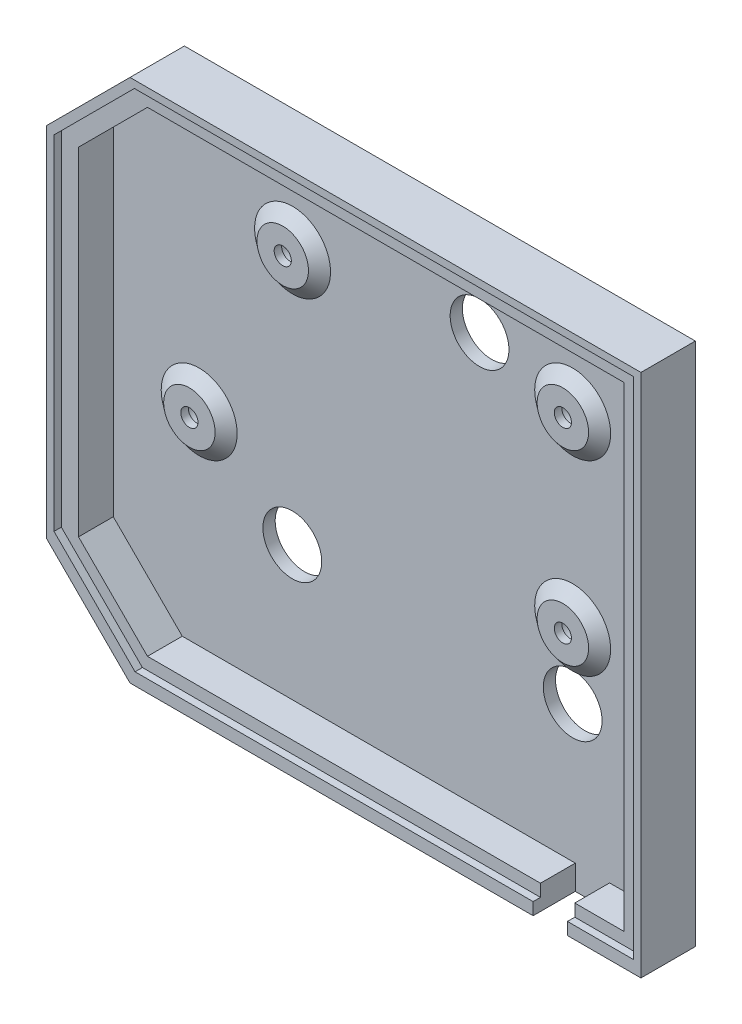
SolidWorks part; units mm, degrees
ref_plane "Plan de face" through (0, 0, 0) normal (0, 0, 1) x (1, 0, 0)
ref_plane "Plan de dessus" through (0, 0, 0) normal (0, 1, 0) x (1, 0, 0)
ref_plane "Plan de droite" through (0, 0, 0) normal (1, 0, 0) x (0, 0, -1)
sketch "Esquisse1" plane through (0, 0, 0) normal (0, 0, 1) x (1, 0, 0)
  line L0 (0, -85) -> (17, -102)
  line L4 (121.25, 5) -> (121.25, -102)
  line L5 (17, 5) -> (0, -12)
  line L7 (121.25, 5) -> (17, 5)
  line L8 (0, -12) -> (0, -85)
  line L9 (17, -102) -> (121.25, -102)
  dimension "D1" = 107
  dimension "D2" = 121.25
  dimension "D3" = 17
  dimension "D4" = 17
  dimension "D5" = 17
  dimension "D6" = 17
extrude "Boss.-Extru.1" add sketch "Esquisse1" along normal blind 2.5
sketch "Esquisse2" plane through (0, 0, 2.5) normal (0, 0, 1) x (1, 0, 0)
  line L0 (0, -12) -> (0, -85) construction
  line L1 (5, 0) -> (116.25, 0) construction
  line L2 (5, 0) -> (5, -97) construction
  line L3 (5, -97) -> (116.25, -97) construction
  line L4 (116.25, 0) -> (116.25, -97) construction
  line L5 (17, -102) -> (121.25, -102) construction
  line L6 (121.25, -102) -> (121.25, 5) construction
  line L7 (121.25, 5) -> (17, 5) construction
  line L9 (5, -82.9289) -> (19.0711, -97)
  line L10 (0, -85) -> (17, -102) construction
  line L11 (5, -14.0711) -> (19.0711, 0)
  line L12 (17, 5) -> (0, -12) construction
  line L13 (116.25, 0) -> (19.0711, 0)
  line L14 (5, -14.0711) -> (5, -82.9289)
  line L16 (121.25, 5) -> (121.25, -102) construction
  line L18 (17, -102) -> (0, -85)
  line L19 (0, -85) -> (0, -12)
  line L20 (0, -12) -> (17, 5)
  line L21 (17, 5) -> (121.25, 5)
  line L40 (121.25, 5) -> (121.25, -102)
  line L41 (121.25, -102) -> (106.25, -102)
  line L42 (106.25, -102) -> (106.25, -97)
  line L43 (106.25, -97) -> (116.25, -97)
  line L44 (116.25, -97) -> (116.25, 0)
  line L48 (19.0711, -97) -> (99.25, -97)
  line L49 (99.25, -97) -> (99.25, -102)
  line L50 (99.25, -102) -> (17, -102)
  point P36 (0, 0)
  dimension "D1" = 5
  dimension "D2" = 5
  dimension "D3" = 5
  dimension "D4" = 5
  dimension "D5" = 5
  dimension "D6" = 7
  dimension "D7" = 15
extrude "Boss.-Extru.2" add sketch "Esquisse2" along normal blind 8.6
sketch "Esquisse4" plane through (0, 0, 2.5) normal (0, 0, 1) x (1, 0, 0)
  line L1 (19.0711, 0) -> (116.25, 0) construction
  line L2 (116.25, 0) -> (116.25, -97) construction
  point P0 (41.57, -17.53)
  point P1 (22.52, -55.63)
  point P2 (98.72, -55.63)
  point P3 (98.72, -17.53)
  dimension "D1" = 17.53
  dimension "D2" = 17.53
  dimension "D3" = 38.1
  dimension "D4" = 57.15
  dimension "D5" = 76.2
ref_axis "Axe1" through (98.72, -55.63, 2.5) along (0, 0, 1)
ref_axis "Axe2" through (22.52, -55.63, 2.5) along (0, 0, 1)
ref_axis "Axe3" through (41.57, -17.53, 2.5) along (0, 0, 1)
ref_axis "Axe4" through (98.72, -17.53, 2.5) along (0, 0, 1)
ref_plane "Plan1" through (0, -55.63, 0) normal (0, -1, 0) x (-1, 0, 0)
ref_plane "Plan2" through (0, -17.53, 0) normal (0, 1, 0) x (1, 0, 0)
sketch "Esquisse9" plane through (0, -55.63, 0) normal (0, -1, 0) x (-1, 0, 0)
  line L0 (-96.97, -2.5) -> (-90.97, -2.5)
  line L1 (-90.97, -2.5) -> (-93.47, -4.5)
  line L2 (-93.47, -4.5) -> (-96.97, -4.5)
  line L3 (-96.97, -4.5) -> (-96.97, -2.5)
  line L4 (-98.72, -2.5) -> (-98.72, -52.3077) construction
  point P0 (-98.5795, 0)
  dimension "D1" = 2
  dimension "D2" = 1.75
  dimension "D3" = 3.5
  dimension "D4" = 6
ref_point "Point1"
ref_point "Point2"
ref_point "Point3"
ref_point "Point4"
revolve "Révolution1" add sketch "Esquisse9" angle 360 about axis through (98.72, -55.63, 2.5) along (0, 0, 1)
sketch "Esquisse11" plane through (0, -55.63, 0) normal (0, -1, 0) x (-1, 0, 0)
  line L0 (-24.27, -2.5) -> (-30.27, -2.5)
  line L1 (-30.27, -2.5) -> (-27.77, -4.5)
  line L2 (-27.77, -4.5) -> (-24.27, -4.5)
  line L3 (-24.27, -4.5) -> (-24.27, -2.5)
  line L4 (-22.52, -2.5) -> (-22.52, -52.3077) construction
  dimension "D1" = 1.75
  dimension "D2" = 3.5
  dimension "D3" = 6
  dimension "D4" = 2
revolve "Révolution2" add sketch "Esquisse11" angle 360 about axis through (22.52, -55.63, 2.5) along (0, 0, 1)
sketch "Esquisse12" plane through (0, -17.53, 0) normal (0, 1, 0) x (1, 0, 0)
  line L0 (96.97, -2.5) -> (90.97, -2.5)
  line L1 (90.97, -2.5) -> (93.47, -4.5)
  line L2 (93.47, -4.5) -> (96.97, -4.5)
  line L3 (96.97, -4.5) -> (96.97, -2.5)
  line L4 (98.72, -2.5) -> (98.72, -52.3077) construction
  dimension "D1" = 1.75
  dimension "D2" = 2
  dimension "D3" = 3.5
  dimension "D4" = 6
revolve "Révolution3" add sketch "Esquisse12" angle 360 about axis through (98.72, -17.53, 2.5) along (0, 0, 1)
sketch "Esquisse13" plane through (0, -17.53, 0) normal (0, 1, 0) x (1, 0, 0)
  line L0 (43.32, -2.5) -> (49.32, -2.5)
  line L1 (49.32, -2.5) -> (46.82, -4.5)
  line L2 (46.82, -4.5) -> (43.32, -4.5)
  line L3 (43.32, -4.5) -> (43.32, -2.5)
  line L4 (41.57, -2.5) -> (41.57, -52.3077) construction
  dimension "D1" = 1.75
  dimension "D2" = 3.5
  dimension "D3" = 6
  dimension "D4" = 2
revolve "Révolution4" add sketch "Esquisse13" angle 360 about axis through (41.57, -17.53, 2.5) along (0, 0, 1)
hole_wizard "Dégagement M31" positions "Esquisse14" profile "Esquisse15" hole size "M3" standard "Ansi Metric" end condition up to next
sketch "Esquisse14" plane through (0, 0, 2.5) normal (0, 0, 1) x (1, 0, 0)
  point P0 (98.72, -55.63)
  point P3 (22.52, -55.63)
  point P6 (98.72, -17.53)
  point P9 (41.57, -17.53)
sketch "Esquisse15" plane through (98.72, -55.63, 2.5) normal (1, 0, 0) x (0, -1, 0)
  line L0 (0, 0) -> (0, 2.5)
  line L1 (0, 2.5) -> (1.8, 2.5)
  line L2 (1.8, 2.5) -> (1.8, 0)
  line L5 (1.8, 0) -> (0, 0)
  line L11 (0, -6.35) -> (0, 107.95) construction
  dimension "Diamètre du perçage jusqu'au prochain" = 3.6
  dimension "Profondeur du perçage jusqu'au prochain" = 2.5
ref_point "Point5"
ref_point "Point6"
ref_point "Point7"
ref_point "Point8"
sketch "Esquisse16" plane through (0, 0, 0) normal (0, 0, -1) x (-1, 0, 0)
  circle A0 centre (-22.52, -55.63) radius 2.7
  circle A1 centre (-98.72, -55.63) radius 2.7
  circle A2 centre (-98.72, -17.53) radius 2.7
  circle A3 centre (-41.57, -17.53) radius 2.7
  dimension "D1" = 5.4
  dimension "D2" = 5.4
  dimension "D3" = 5.4
  dimension "D4" = 5.4
extrude "Enlèv. mat.-Extru.2" cut sketch "Esquisse16" against normal blind 3
sketch "Esquisse17" plane through (0, 0, 11.1) normal (0, 0, 1) x (1, 0, 0)
  line L1 (119.75, -99.5) -> (1.5, -99.5) construction
  line L2 (119.75, -99.5) -> (119.75, 3.5)
  line L3 (119.75, 3.5) -> (1.5, 3.5) construction
  line L4 (1.5, -99.5) -> (1.5, 3.5) construction
  line L6 (0, -12) -> (0, -85) construction
  line L7 (121.25, 5) -> (17, 5) construction
  line L8 (-697.163, -711.5671) -> (34658.1761, 34643.7719) construction
  line L9 (17, 5) -> (0, -12) construction
  line L10 (119.75, 3.5) -> (17.9042, 3.5)
  line L11 (17.9042, 3.5) -> (1.5, -12.9042)
  line L18 (15.5687, -97.0332) -> (-9.8376, -71.6268) construction
  line L19 (0, -85) -> (17, -102) construction
  line L20 (119.75, -99.5) -> (18.0355, -99.5)
  line L21 (18.0355, -99.5) -> (1.5, -82.9645)
  line L24 (1.5, -12.9042) -> (1.5, -82.9645)
  line L25 (106.25, -102) -> (121.25, -102) construction
  line L26 (121.25, -102) -> (121.25, 5) construction
  dimension "D1" = 2.5
  dimension "D2" = 1.5
  dimension "D3" = 1.5
  dimension "D4" = 1.5
  dimension "D5" = 2.5
  dimension "D6" = 1.7
extrude "Enlèv. mat.-Extru.3" cut sketch "Esquisse17" against normal blind 1.5
sketch "Esquisse20" plane through (0, 0, 2.5) normal (0, 0, 1) x (1, 0, 0)
  circle A0 centre (98.72, -69.13) radius 6
  circle A1 centre (41.52, -69.63) radius 6
  circle A2 centre (79.72, -13.03) radius 6
  dimension "D1" = 13.5
  dimension "D3" = 19
  dimension "D5" = 19
  dimension "D2" = 0
  dimension "D4" = 14
  dimension "D6" = 4.5
extrude "Enlèv. mat.-Extru.4" cut sketch "Esquisse20" against normal blind 10 and the other way blind 10
chamfer "Chanfrein3" distance 1 angle 30 4 edges at (38.87, -17.53, 3) (96.02, -17.53, 3) (96.02, -55.63, 3) (19.82, -55.63, 3) first distance on face at (38.87, -17.53, 3) first distance on face at (96.97, -17.53, 3) first distance on face at (96.02, -55.63, 3) first distance on face at (20.77, -55.63, 3)
equation "\"r_ext\"= 5.4"
equation "\"D1@Esquisse16\"=\"r_ext\""
equation "\"D2@Esquisse16\"=\"r_ext\""
equation "\"D3@Esquisse16\"=\"r_ext\""
equation "\"D4@Esquisse16\"=\"r_ext\""
